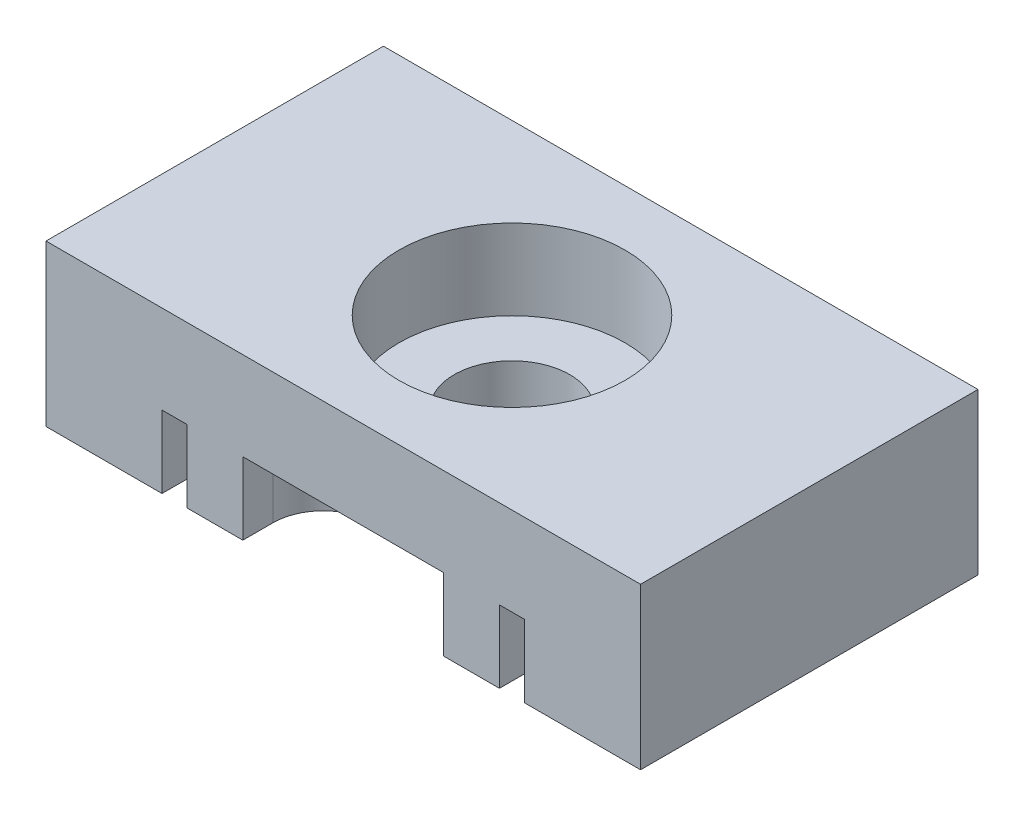
SolidWorks part; units mm, degrees
material "2024 Alloy"
ref_plane "Front Plane" through (0, 0, 0) normal (0, 0, 1) x (1, 0, 0)
ref_plane "Top Plane" through (0, 0, 0) normal (0, 1, 0) x (1, 0, 0)
ref_plane "Right Plane" through (0, 0, 0) normal (1, 0, 0) x (0, 0, -1)
sketch "Sketch1" plane through (0, 0, 0) normal (0, 1, 0) x (1, 0, 0)
  line L1 (-9.398, -5.334) -> (9.398, -5.334)
  line L2 (-9.398, -5.334) -> (-9.398, 5.334)
  line L3 (-9.398, 5.334) -> (9.398, 5.334)
  line L4 (9.398, -5.334) -> (9.398, 5.334)
  line L5 (-9.398, -5.334) -> (9.398, 5.334) construction
  line L6 (-9.398, 5.334) -> (9.398, -5.334) construction
  point P0 (0, 0)
  dimension "D1" = 18.796
  dimension "D2" = 10.668
extrude "Base" add sketch "Sketch1" along normal blind 5.08
sketch "Sketch2" plane through (0, 0, 0) normal (0, -1, 0) x (1, 0, 0)
  line L0 (-5.334, 5.334) -> (-5.334, 3.8608) construction
  line L1 (-9.398, 5.334) -> (9.398, 5.334) construction
  line L2 (-4.9371, 5.334) -> (-4.9371, 3.8608)
  line L3 (-5.7309, 5.334) -> (-5.7309, 3.8608)
  line L4 (5.334, 5.334) -> (5.334, 3.8608) construction
  line L5 (5.7309, 5.334) -> (5.7309, 3.8608)
  line L6 (4.9371, 5.334) -> (4.9371, 3.8608)
  line L7 (0, 0) -> (0, 225.9023) construction
  arc A0 (-4.9371, 5.334) -> (-5.7309, 5.334) centre (-5.334, 5.334) ccw
  arc A1 (-5.7309, 3.8608) -> (-4.9371, 3.8608) centre (-5.334, 3.8608) ccw
  arc A2 (5.7309, 5.334) -> (4.9371, 5.334) centre (5.334, 5.334) ccw
  arc A3 (4.9371, 3.8608) -> (5.7309, 3.8608) centre (5.334, 3.8608) ccw
  point P4 (-5.334, 4.5974)
  point P9 (5.334, 4.5974)
  dimension "D1" = 0.7937
  dimension "D2" = 10.668
  dimension "D3" = 1.4732
extrude "BoxSlots" cut sketch "Sketch2" against normal blind 2.286
hole_wizard "MoutingHole" positions "Sketch6" profile "Sketch5" counterbore size "#6" standard "ANSI Inch" end condition through all
sketch "Sketch6" plane through (0, 5.08, 0) normal (0, 1, 0) x (1, 0, 0)
  point P0 (0, 0)
sketch "Sketch5" plane through (0, 5.08, 0) normal (1, 0, 0) x (0, 0, 1)
  line L0 (0, 0) -> (0, 5.08)
  line L1 (0, 5.08) -> (1.8288, 5.08)
  line L3 (1.8288, 5.08) -> (1.8288, 2.54)
  line L4 (1.8288, 2.54) -> (3.5725, 2.54)
  line L5 (3.5725, 2.54) -> (3.5725, 0)
  line L7 (3.5725, 0) -> (0, 0)
  line L11 (0, -6.35) -> (0, 107.95) construction
  dimension "Thru Hole Dia." = 3.6576
  dimension "Thru Hole Depth" = 5.08
  dimension "C'Bore Dia." = 7.145
  dimension "C'Bore Depth" = 2.54
sketch "Sketch7" plane through (0, 0, 0) normal (0, -1, 0) x (1, 0, 0)
  line L0 (-4.9371, 5.334) -> (4.9371, 5.334) construction
  line L1 (-3.175, 5.334) -> (3.175, 5.334)
  line L2 (-3.175, 5.334) -> (-3.175, 4.3815)
  line L3 (-1.5875, 2.794) -> (1.5875, 2.794)
  line L4 (3.175, 5.334) -> (3.175, 4.3815)
  line L5 (-3.175, 5.334) -> (3.175, 2.794) construction
  line L6 (-3.175, 2.794) -> (3.175, 5.334) construction
  arc A0 (-1.5875, 2.794) -> (-3.175, 4.3815) centre (-1.5875, 4.3815) cw
  arc A1 (1.5875, 2.794) -> (3.175, 4.3815) centre (1.5875, 4.3815) ccw
  point P0 (0, 4.064)
  dimension "D3" = 1.5875
  dimension "D1" = 6.35
  dimension "D2" = 2.54
extrude "Cut-Extrude1" cut sketch "Sketch7" against normal blind 2.286
